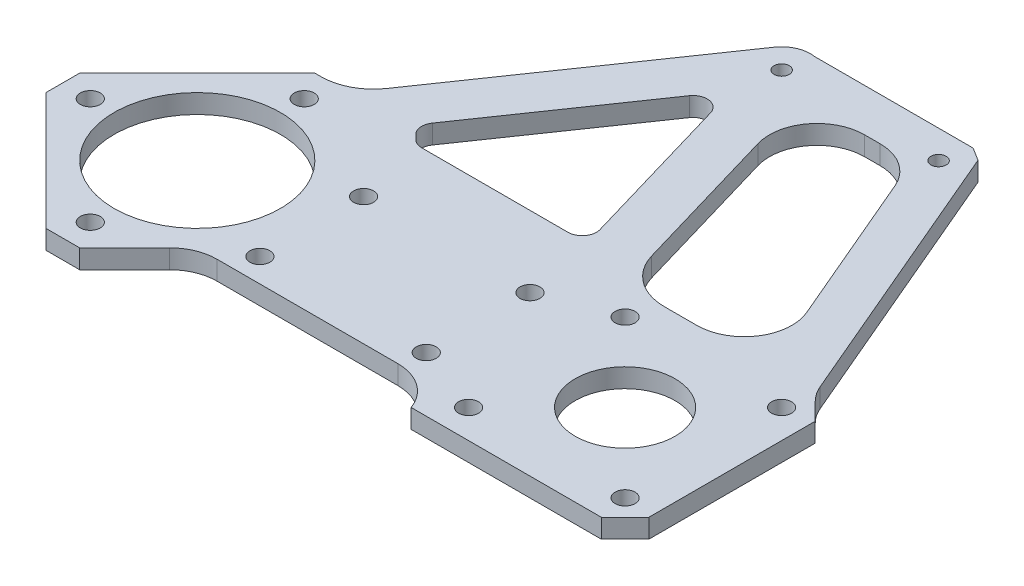
SolidWorks part; units mm, degrees
ref_plane "前视基准面" through (0, 0, 0) normal (0, 0, 1) x (1, 0, 0)
ref_plane "上视基准面" through (0, 0, 0) normal (0, 1, 0) x (1, 0, 0)
ref_plane "右视基准面" through (0, 0, 0) normal (1, 0, 0) x (0, 0, -1)
sketch "草图1" plane through (0, 0, 0) normal (0, 1, 0) x (1, 0, 0)
  line L0 (0, 0) -> (-31.8198, 0) construction
  line L1 (0, 31.8198) -> (-31.8198, 0)
  line L2 (-31.8198, 0) -> (0, -31.8198)
  line L3 (0, -31.8198) -> (15.9099, -15.9099)
  line L4 (15.9099, 15.9099) -> (0, 31.8198)
  line L5 (0, 0) -> (90, 0) construction
  line L6 (0, 0) -> (45, 77.9423) construction
  line L7 (45, 77.9423) -> (90, 0) construction
  line L8 (15.9099, 15.9099) -> (67.5, 15.9099)
  line L9 (15.9099, -15.9099) -> (67.5, -15.9099)
  line L10 (90, 0) -> (67.5, -22.5) construction
  line L11 (67.5, 22.5) -> (67.5, 15.9099)
  line L12 (67.5, -22.5) -> (112.5, -22.5)
  line L13 (112.5, -22.5) -> (112.5, 22.5)
  line L14 (112.5, 22.5) -> (67.5, 22.5)
  line L15 (67.5, -15.9099) -> (67.5, -22.5)
  line L16 (0, 0) -> (15.9099, 15.9099) construction
  line L17 (0, 0) -> (15.9099, -15.9099) construction
  circle A0 centre (0, 14) radius 2.1
  circle A1 centre (14, 0) radius 2.1
  circle A2 centre (0, -14) radius 2.1
  circle A3 centre (-14, 0) radius 2.1
  circle A4 centre (0, 0) radius 22.5 construction
  arc A5 (45, -77.9423) -> (45, 77.9423) centre (0, 0) ccw construction
  arc A6 (45, 77.9423) -> (45, -77.9423) centre (90, 0) ccw construction
  circle A7 centre (90, 0) radius 10.5
  circle A8 centre (90, 0) radius 22.5 construction
  circle A9 centre (0, 22.5) radius 2.1
  circle A11 centre (0, -22.5) radius 2.1
  circle A12 centre (0, 0) radius 10
  circle A13 centre (0, 0) radius 14 construction
  circle A14 centre (-22.5, 0) radius 2.1
  dimension "D1" = 4.2
  dimension "D2" = 20
  dimension "D3" = 4.2
  dimension "D4" = 4.2
  dimension "D5" = 4.2
  dimension "D6" = 45
  dimension "D9" = 180
  dimension "D10" = 180
  dimension "D11" = 21
  dimension "D14" = 4.2
  dimension "D15" = 4.2
  dimension "D17" = 4.2
  dimension "D7" = 180
  dimension "D8" = 90
  dimension "D12" = 135
  dimension "D13" = 45
extrude "凸台-拉伸1" add sketch "草图1" along normal blind 4
chamfer "倒角1" distance 5 angle 45 5 edges at (112.5, 2, 22.5) (112.5, 2, -22.5) (0, 2, 31.8198) (-31.8198, 2, 0) (0, 2, -31.8198)
fillet "圆角1" radius 10 4 edges at (15.9099, 2, -15.9099) (15.9099, 2, 15.9099) (67.5, 2, 15.9099) (67.5, 2, -15.9099)
sketch "草图2" plane through (0, 0, 0) normal (0, -1, 0) x (1, 0, 0)
  line L0 (39.0757, 15.9099) -> (39.0757, 10.9099) construction
  line L1 (20.052, 15.9099) -> (58.0993, 15.9099) construction
  line L2 (39.0757, 10.9099) -> (24.0757, 10.9099) construction
  line L3 (39.0757, 10.9099) -> (59.0757, 10.9099) construction
  line L4 (110, 20) -> (90, 0) construction
  line L5 (112.5, 17.5) -> (107.5, 22.5) construction
  line L6 (110, -20) -> (90, 0) construction
  line L7 (107.5, -22.5) -> (112.5, -17.5) construction
  line L8 (90, 22.5) -> (90, -22.5) construction
  line L9 (67.5, 22.5) -> (107.5, 22.5) construction
  line L10 (107.5, -22.5) -> (67.5, -22.5) construction
  line L11 (70, -20) -> (90, 0) construction
  line L12 (70, 20) -> (90, 0) construction
  line L13 (0, 0) -> (90, 0) construction
  line L14 (39.0757, -10.9099) -> (59.0757, -10.9099) construction
  line L15 (39.0757, -10.9099) -> (24.0757, -10.9099) construction
  line L16 (39.0757, -15.9099) -> (39.0757, -10.9099) construction
  circle A0 centre (106.4645, 16.4645) radius 2.1
  circle A1 centre (106.4645, -16.4645) radius 2.1
  circle A2 centre (73.5355, -16.4645) radius 2.1
  circle A3 centre (73.5355, 16.4645) radius 2.1
  circle A4 centre (24.0757, 10.9099) radius 2.1
  circle A5 centre (59.0757, 10.9099) radius 2.1
  circle A6 centre (59.0757, -10.9099) radius 2.1
  circle A7 centre (24.0757, -10.9099) radius 2.1
  dimension "D3" = 4.2
  dimension "D4" = 4.2
  dimension "D5" = 20
  dimension "D6" = 15
  dimension "D8" = 4.2
  dimension "D9" = 4.2
  dimension "D1" = 5
  dimension "D2" = 5
  dimension "D7" = 5
extrude "切除-拉伸1" cut sketch "草图2" against normal blind 10
sketch "草图3" plane through (0, 4, 0) normal (0, 1, 0) x (1, 0, 0)
  line L0 (0, 0) -> (90, 0) construction
  line L1 (45, 0) -> (45, 77.9423) construction
  line L2 (3.5355, 28.2843) -> (40.0576, 81.3442)
  line L3 (67.5, 22.5) -> (50.7578, 79.6297)
  line L4 (12.981, 18.8388) -> (3.5355, 28.2843) construction
  line L5 (58.0993, 15.9099) -> (20.052, 15.9099) construction
  line L6 (12.981, 18.8388) -> (3.5355, 28.2843)
  line L7 (58.0993, 15.9099) -> (20.052, 15.9099)
  line L8 (16.4918, 29.4702) -> (43.5266, 68.7468)
  line L9 (56.0801, 25.9099) -> (43.5266, 68.7468)
  line L10 (56.0801, 25.9099) -> (20.052, 25.9099)
  line L11 (20.052, 25.9099) -> (16.4918, 29.4702)
  circle A0 centre (45, 77.9423) radius 1.6
  arc A1 (50.7578, 79.6297) -> (40.0576, 81.3442) centre (45, 77.9423) ccw
  arc A2 (12.981, 18.8388) -> (20.052, 15.9099) centre (20.052, 25.9099) ccw construction
  arc A3 (58.0993, 15.9099) -> (67.5, 22.5) centre (58.0993, 25.9099) ccw construction
  arc A4 (12.981, 18.8388) -> (20.052, 15.9099) centre (20.052, 25.9099) ccw
  arc A5 (58.0993, 15.9099) -> (67.5, 22.5) centre (58.0993, 25.9099) ccw
  arc A6 (43.5266, 68.7468) -> (43.5266, 68.7468) centre (43.5266, 68.7468) ccw
  arc A7 (56.0801, 25.9099) -> (56.0801, 25.9099) centre (56.0801, 25.9099) ccw
  arc A8 (20.052, 25.9099) -> (20.052, 25.9099) centre (20.052, 25.9099) ccw
  dimension "D1" = 3.2
  dimension "D2" = 12
  dimension "D3" = 10
extrude "凸台-拉伸2" add sketch "草图3" against normal blind 4
fillet "圆角2" radius 3 4 edges at (20.052, 2, -25.9099) (16.4918, 2, -29.4702) (56.0801, 2, -25.9099) (43.5266, 2, -68.7468)
fillet "圆角3" radius 11 2 edges at (3.5355, 2, -28.2843) (67.5, 2, -22.5)
sketch "草图4" plane through (0, 4, 0) normal (0, 1, 0) x (1, 0, 0)
  line L0 (45.9493, 83.8667) -> (81.3477, 83.8667)
  line L3 (81.3477, 83.8667) -> (107.5, 22.5)
  line L4 (52.1537, 74.8667) -> (75.4, 74.8667)
  line L5 (75.4, 74.8667) -> (97.7168, 22.5)
  line L6 (107.5, 22.5) -> (75.739, 22.5) construction
  line L7 (73.0682, 80.3383) -> (99.2205, 18.9716) construction
  line L8 (45.9493, 74.8667) -> (90, 74.8667) construction
  line L9 (107.5, 22.5) -> (97.7168, 22.5)
  line L10 (65.183, 30.4065) -> (50.7578, 79.6297) construction
  line L11 (52.1537, 74.8667) -> (50.7578, 79.6297)
  line L12 (45.9493, 83.8667) -> (90, 83.8667) construction
  arc A0 (50.7578, 79.6297) -> (40.0576, 81.3442) centre (45, 77.9423) ccw construction
  circle A2 centre (78, 77.9423) radius 1.6
  arc A3 (50.7578, 79.6297) -> (45.9493, 83.8667) centre (45, 77.9423) ccw
  dimension "D1" = 33
extrude "凸台-拉伸3" add sketch "草图4" against normal blind 4
fillet "圆角4" radius 10 3 edges at (75.4, 2, -74.8667) (97.7168, 2, -22.5) (52.1537, 2, -74.8667)
chamfer "倒角2" distance 2 angle 32 1 edges at (81.3477, 2, -83.8667) first distance on face at (63.6485, 2, -83.8667)
fillet "圆角5" radius 10 1 edges at (107.5, 2, -22.5)
sketch "草图5" plane through (0, 4, 0) normal (0, 1, 0) x (1, 0, 0)
  circle A0 centre (0, 0) radius 17.5
  dimension "D1" = 35
extrude "切除-拉伸2" cut sketch "草图5" against normal blind 10
